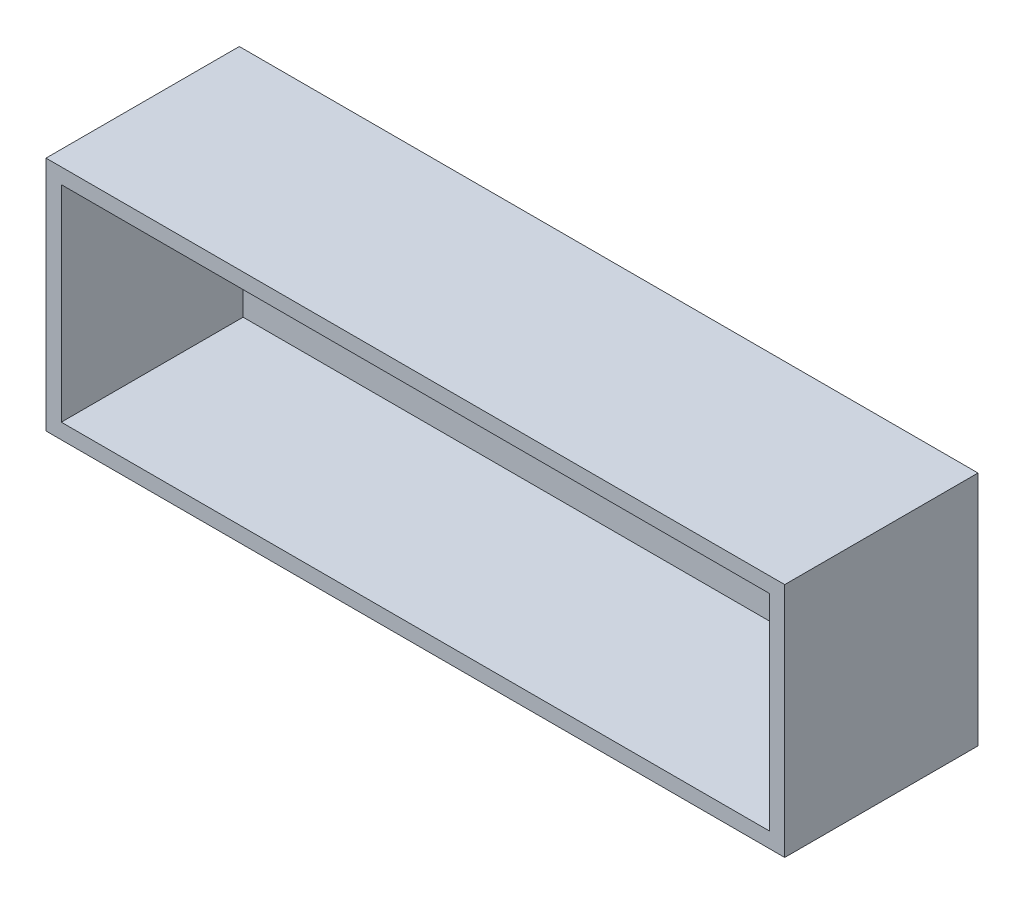
SolidWorks part; units mm, degrees
ref_plane "Front Plane" through (0, 0, 0) normal (0, 0, 1) x (1, 0, 0)
ref_plane "Top Plane" through (0, 0, 0) normal (0, 1, 0) x (1, 0, 0)
ref_plane "Right Plane" through (0, 0, 0) normal (1, 0, 0) x (0, 0, -1)
sketch "Sketch1" plane through (0, 0, 0) normal (0, 0, 1) x (1, 0, 0)
  line L1 (-37, -10.75) -> (37, -10.75)
  line L2 (-37, -10.75) -> (-37, 10.75)
  line L3 (-37, 10.75) -> (37, 10.75)
  line L4 (37, -10.75) -> (37, 10.75)
  line L5 (-37, -10.75) -> (37, 10.75) construction
  line L6 (-37, 10.75) -> (37, -10.75) construction
  line L7 (-38.6, -12.35) -> (38.6, -12.35)
  line L8 (-38.6, -12.35) -> (-38.6, 12.35)
  line L9 (-38.6, 12.35) -> (38.6, 12.35)
  line L10 (38.6, -12.35) -> (38.6, 12.35)
  line L11 (-38.6, -12.35) -> (38.6, 12.35) construction
  line L12 (-38.6, 12.35) -> (38.6, -12.35) construction
  point P0 (0, 0)
  point P6 (0, 0)
  dimension "D1" = 21.5
  dimension "D2" = 74
  dimension "D3" = 1.6
  dimension "D4" = 1.6
extrude "Boss-Extrude1" add sketch "Sketch1" along normal blind 19
extrude "Boss-Extrude2" add sketch "Sketch1<2>" against normal blind 1.2 contours L7 L10 L9 L8 L4 L1 L2 L3 | L1 L4 L3 L2 region at (0, 0, 0) region at (-37.7894, 0, 0)
sketch "Sketch1<2>" plane through (0, 0, 0) normal (0, 0, 1) x (1, 0, 0) same geometry as "Sketch1"
